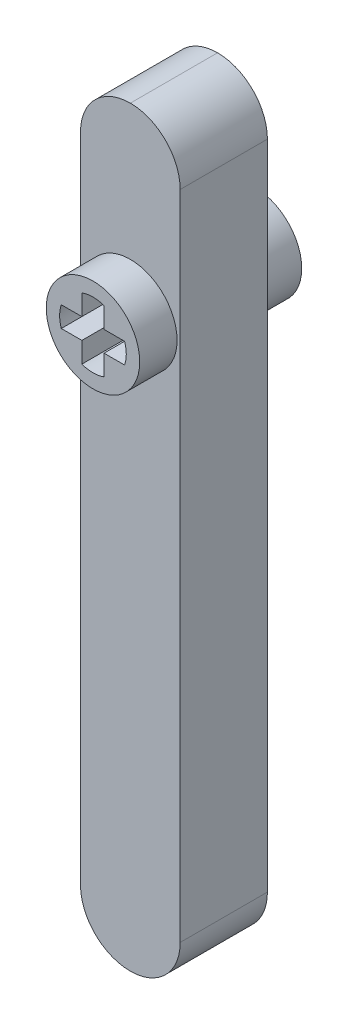
SolidWorks part; units mm, degrees
ref_plane "Front Plane" through (0, 0, 0) normal (0, 0, 1) x (1, 0, 0)
ref_plane "Top Plane" through (0, 0, 0) normal (0, 1, 0) x (1, 0, 0)
ref_plane "Right Plane" through (0, 0, 0) normal (1, 0, 0) x (0, 0, -1)
sketch "Sketch1" plane through (0, 0, 0) normal (0, 0, 1) x (1, 0, 0)
  line L0 (4, 25.4) -> (4, 34.925)
  line L2 (-4, 25.4) -> (-4, -25.4)
  line L3 (-4, -25.4) -> (4, -25.4)
  line L4 (4, 25.4) -> (4, -25.4)
  line L5 (-4, 25.4) -> (4, -25.4) construction
  line L6 (-4, -25.4) -> (4, 25.4) construction
  line L7 (4, 34.925) -> (-4, 34.925)
  line L8 (-4, 34.925) -> (-4, 25.4)
  line L9 (-4, 25.4) -> (4, 25.4) construction
  point P0 (0, 0)
  dimension "D1" = 8
  dimension "D2" = 50.8
  dimension "D3" = 34.925
extrude "Boss-Extrude1" add sketch "Sketch1" along normal blind 7
fillet "Fillet1" radius 4 4 edges at (-4, -25.4, 3.5) (4, -25.4, 3.5) (4, 34.925, 3.5) (-4, 34.925, 3.5)
sketch "Sketch2" plane through (0, 0, 7) normal (0, 0, 1) x (1, 0, 0)
  circle A0 centre (0, 20.32) radius 3.75
  dimension "D1" = 7.5
  dimension "D2" = 20.32
extrude "Boss-Extrude2" add sketch "Sketch2" along normal blind 3 and the other way blind 10
sketch "Sketch3" plane through (0, 0, -3) normal (0, 0, -1) x (-1, 0, 0)
  line L10 (-0.889, 21.1455) -> (-0.889, 22.7965)
  line L11 (0.889, 22.7965) -> (0.889, 21.1455)
  line L20 (-0.889, 21.1455) -> (0.889, 21.1455) construction
  line L21 (-0.889, 21.1455) -> (-0.889, 19.4945) construction
  line L22 (-0.889, 21.1455) -> (-2.54, 21.1455)
  line L23 (-2.54, 19.4945) -> (-0.889, 19.4945)
  line L24 (-0.889, 19.4945) -> (-0.889, 17.8435)
  line L25 (0.889, 17.8435) -> (0.889, 19.4945)
  line L26 (0.889, 19.4945) -> (2.54, 19.4945)
  line L27 (0.889, 21.1455) -> (2.54, 21.1455)
  line L28 (2.54, 21.1455) -> (0.889, 21.1455)
  circle A10 centre (0, 20.32) radius 2.5157 construction
  arc A11 (-0.889, 22.7965) -> (0.889, 22.7965) centre (0, 20.3532) cw
  arc A12 (-2.54, 21.1455) -> (-2.54, 19.4945) centre (-0.0745, 20.32) ccw
  arc A13 (-0.889, 17.8435) -> (0.889, 17.8435) centre (0, 20.2868) ccw
  arc A14 (2.54, 21.1455) -> (2.54, 19.4945) centre (0.0745, 20.32) cw
  circle A15 centre (0, 20.32) radius 3.75 construction
  point P6 (0, 21.1455)
  point P10 (0, 0)
  point P18 (-1.0808, 20.9709)
  point P21 (-2.6745, 20.32)
  point P22 (0, 0)
  point P23 (0, 0)
  point P25 (0, 0)
  point P26 (-2.3517, 21.0514)
  point P27 (2.278, 21.1455)
  point P28 (0, 17.6868)
  point P29 (0, 0)
  dimension "D2" = 1.778
  dimension "D3" = 2.6
  dimension "D1" = 1.651
extrude "Cut-Extrude1" cut sketch "Sketch3" against normal through all contours L11 A11 L10 L25 region at (0, 20.32, -3)
